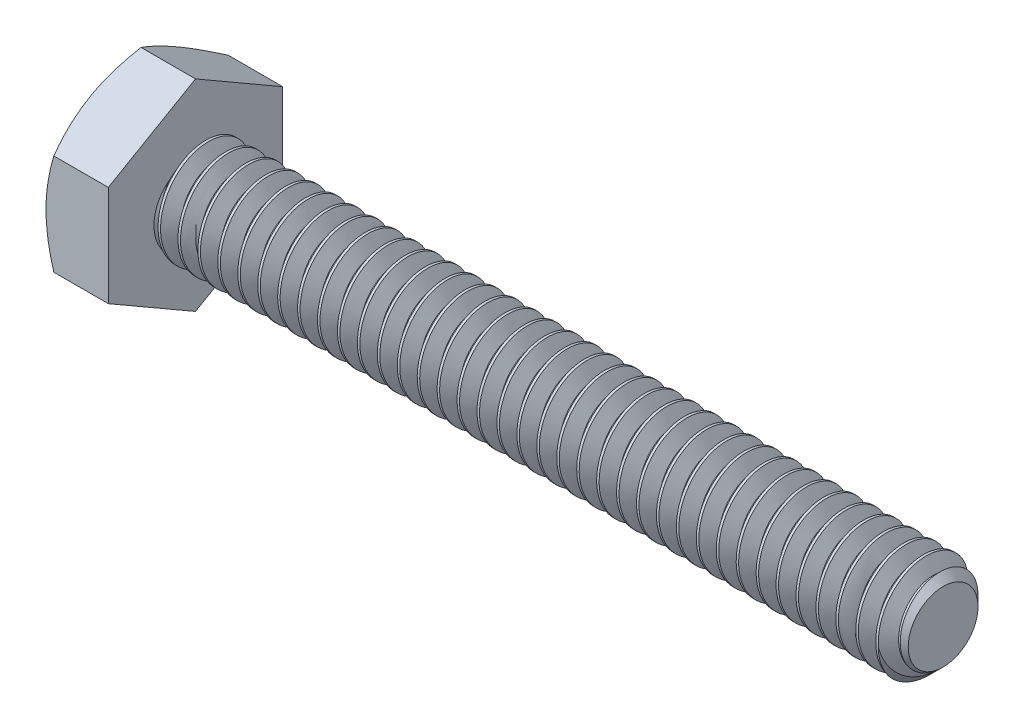
SolidWorks part; units mm, degrees
ref_plane "Front Plane" through (0, 0, 0) normal (0, 0, 1) x (1, 0, 0)
ref_plane "Top Plane" through (0, 0, 0) normal (0, 1, 0) x (1, 0, 0)
ref_plane "Right Plane" through (0, 0, 0) normal (1, 0, 0) x (0, 0, -1)
sketch "Sketch1" plane through (0, 0, 0) normal (0, 0, 1) x (1, 0, 0)
  line L0 (-25.7969, 0) -> (25.7969, 0) construction
  line L1 (25.7969, 3.175) -> (25.7969, -3.175) construction
  line L2 (-21.8281, 5.5563) -> (-21.8281, -5.5563) construction
  line L3 (-25.7969, 5.5562) -> (-25.7969, -5.5562) construction
  point P9 (-21.8281, 0)
  point P10 (21.3519, -3.175)
  dimension "Screw Dia" = 6.35
  dimension "Hex" = 11.1125
  dimension "Head Ht" = 3.9688
  dimension "Screw Lenght" = 47.625
  dimension "D1" = 4.445
ref_plane "Plane2" through (25.7969, 0, 0) normal (1, 0, 0) x (0, 0, -1)
sketch "Sketch5" plane through (25.7969, 0, 0) normal (1, 0, 0) x (0, 0, -1)
  circle A0 centre (0, 0) radius 3.175
extrude "Boss-Extrude3" add sketch "Sketch5" against normal up to vertex (47.625 mm away) up to point (-21.8281, 0, 0)
sketch "Sketch9" plane through (25.7969, 0, 0) normal (1, 0, 0) x (0, 0, -1)
  circle A1 centre (0, 0) radius 3.175
  circle A2 centre (0, 0) radius 3.175
  dimension "D1" = 0
curve "Helix/Spiral1" pitch 1.27 height 48.895 turns 38.5 parameters "Pitch"=1.27
chamfer "Chamfer1" distance 0.9525 angle 45 1 edges at (25.7969, 0, -3.175)
sketch "Sketch10" plane through (0, 0, 0) normal (0, 0, 1) x (1, 0, 0)
  line L0 (25.7969, 3.175) -> (26.2731, 2.3501)
  line L1 (26.2731, 2.3501) -> (26.4319, 2.3501)
  line L2 (26.4319, 2.3501) -> (26.9081, 3.175)
  line L3 (25.7969, 3.175) -> (26.9081, 3.175)
  line L4 (26.3525, 3.175) -> (26.3525, 2.3501) construction
  line L5 (26.035, 2.7626) -> (26.67, 2.7626) construction
  dimension "D1" = 60
  dimension "D2" = 0.1588
  dimension "D3" = 0.635
sweep "Cut-Sweep1" cut profiles "Sketch10" path "Helix/Spiral1"
sketch "Sketch6" plane through (-21.8281, 0, 0) normal (-1, 0, 0) x (0, 0, 1)
  line L0 (0, 5.5563) -> (0, -5.5563) construction
  line L1 (5.5562, 3.2079) -> (0, 6.4158)
  line L2 (0, 6.4158) -> (-5.5562, 3.2079)
  line L3 (-5.5562, 3.2079) -> (-5.5562, -3.2079)
  line L4 (-5.5562, -3.2079) -> (0, -6.4158)
  line L5 (0, -6.4158) -> (5.5563, -3.2079)
  line L6 (5.5563, -3.2079) -> (5.5562, 3.2079)
  circle A0 centre (0, 0) radius 5.5563 construction
extrude "Boss-Extrude4" add sketch "Sketch6" along normal up to vertex (3.9688 mm away) up to point (-25.7969, -5.5562, 0)
sketch "Sketch7" plane through (-25.7969, 0, 0) normal (-1, 0, 0) x (0, 0, 1)
  circle A0 centre (0, 0) radius 5.5563 construction
  circle A1 centre (0, 0) radius 5.5563
sketch "Sketch8" plane through (-25.7969, 0, 0) normal (-1, 0, 0) x (0, 0, 1)
  circle A0 centre (0, 0) radius 5.5563 construction
  circle A1 centre (0, 0) radius 5.5563
extrude "Cut-Extrude3" cut sketch "Sketch8" against normal through all draft 60 flip side to cut
equation "\"D2@Sketch10\" = \"Pitch@Helix/Spiral1\"*.125"
equation "\"D3@Sketch10\" = \"Pitch@Helix/Spiral1\"*.5"
equation "\"D3@Helix/Spiral1\" = \"Screw Lenght@Sketch1\"+\"Pitch@Helix/Spiral1\""
equation "\"D1@Chamfer1\" = \"Pitch@Helix/Spiral1\"*.75"
equation "\"D1@Sketch1\" = \"Pitch@Helix/Spiral1\"*3.5"
